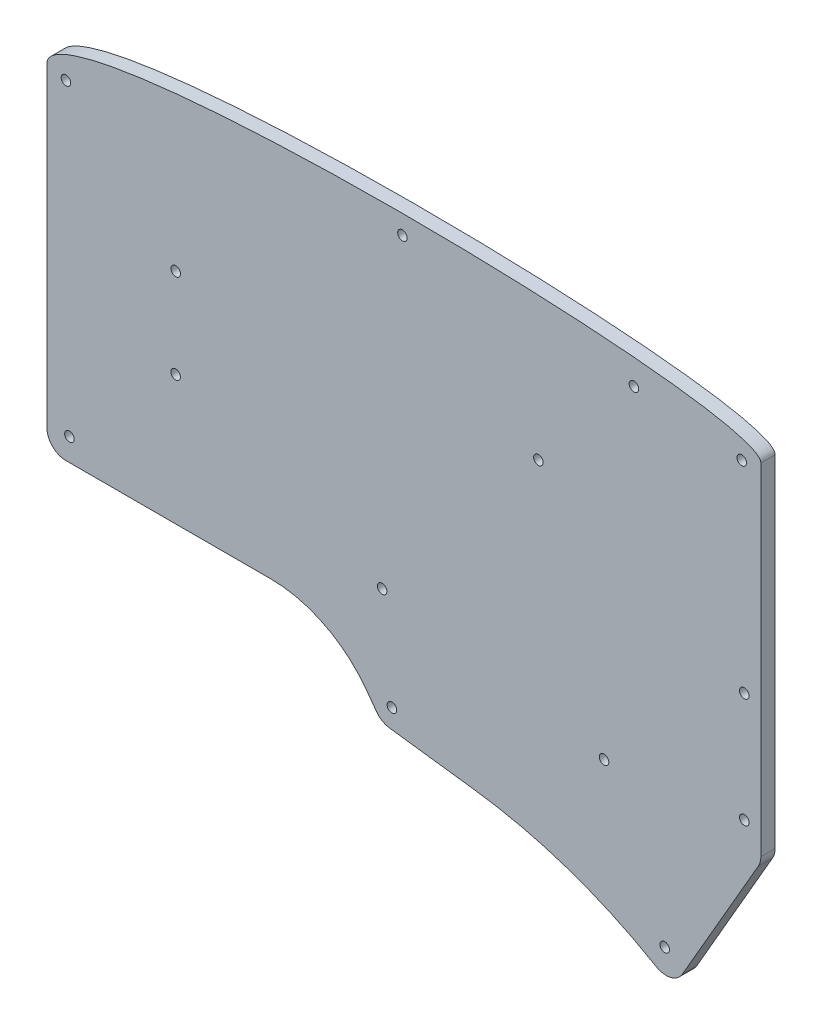
SolidWorks part; units mm, degrees
ref_plane "Front Plane" through (0, 0, 0) normal (0, 0, 1) x (1, 0, 0)
ref_plane "Top Plane" through (0, 0, 0) normal (0, 1, 0) x (1, 0, 0)
ref_plane "Right Plane" through (0, 0, 0) normal (1, 0, 0) x (0, 0, -1)
sketch "Model" plane through (0, 0, 0) normal (0, 0, 1) x (1, 0, 0)
  line L0 (-21.8431, 7.4481) -> (-8.6148, 30.3792)
  line L1 (-38.0636, 15.3297) -> (-23.771, 7.0696)
  line L2 (-75.3888, 20.2293) -> (-38.7189, 15.4592)
  line L3 (-86.2854, 34.8343) -> (-75.7419, 20.3766)
  line L4 (-29.1405, 92.9799) -> (-29.1405, 91.7303)
  line L5 (-8.8891, 91.2299) -> (-28.6402, 91.2299)
  line L6 (-8.3888, 90.7295) -> (-8.3888, 31.2555)
  line L7 (-86.6385, 34.9791) -> (-141.6396, 34.9791)
  line L8 (-142.1399, 90.7295) -> (-142.1399, 35.4795)
  line L9 (-104.6394, 91.2299) -> (-141.6396, 91.2299)
  line L10 (-104.139, 95.4793) -> (-104.139, 91.7303)
  line L11 (-85.6402, 95.9797) -> (-103.6387, 95.9797)
  line L12 (-85.1399, 97.7297) -> (-85.1399, 96.4801)
  line L13 (-67.6393, 98.2301) -> (-84.6395, 98.2301)
  line L14 (-67.1389, 96.4801) -> (-67.1389, 97.7297)
  line L15 (-48.6401, 95.9797) -> (-66.6385, 95.9797)
  line L16 (-48.1397, 93.9807) -> (-48.1397, 95.4793)
  line L17 (-29.6384, 93.4803) -> (-47.6393, 93.4803)
  line L18 (135.1563, 30.6526) -> (116.2359, 41.5721)
  line L19 (123.1828, 7.2669) -> (135.5373, 28.7222)
  line L20 (106.9623, 15.1485) -> (121.2549, 6.8884)
  line L21 (69.6371, 20.0481) -> (106.307, 15.278)
  line L22 (58.7405, 34.6531) -> (69.284, 20.1955)
  line L23 (115.8854, 92.7987) -> (115.8828, 42.2376)
  line L24 (58.3874, 34.7979) -> (3.3863, 34.7979)
  line L25 (2.886, 90.5483) -> (2.886, 35.2983)
  line L26 (40.3865, 91.0487) -> (3.3863, 91.0487)
  line L27 (40.8869, 95.2981) -> (40.8869, 91.5491)
  line L28 (59.3857, 95.7985) -> (41.3872, 95.7985)
  line L29 (59.886, 97.5485) -> (59.886, 96.2989)
  line L30 (77.3866, 98.0489) -> (60.3864, 98.0489)
  line L31 (77.887, 96.2989) -> (77.887, 97.5485)
  line L32 (96.3858, 95.7985) -> (78.3874, 95.7985)
  line L33 (96.8862, 93.7995) -> (96.8862, 95.2981)
  line L34 (115.3875, 93.2991) -> (97.3866, 93.2991)
  line L35 (20.1915, -96.2476) -> (6.9631, -73.3165)
  line L36 (36.4119, -88.366) -> (22.1193, -96.6261)
  line L37 (73.7371, -83.4663) -> (37.0672, -88.2365)
  line L38 (84.6337, -68.8614) -> (74.0902, -83.319)
  line L39 (27.4889, -10.7157) -> (27.4889, -11.9654)
  line L40 (7.2375, -12.4658) -> (26.9885, -12.4658)
  line L41 (6.7371, -12.9662) -> (6.7371, -72.4402)
  line L42 (84.9868, -68.7166) -> (139.9879, -68.7166)
  line L43 (140.4883, -12.9662) -> (140.4883, -68.2162)
  line L44 (102.9878, -12.4658) -> (139.9879, -12.4658)
  line L45 (102.4874, -8.2164) -> (102.4874, -11.9654)
  line L46 (83.9886, -7.716) -> (101.987, -7.716)
  line L47 (83.4882, -5.9659) -> (83.4882, -7.2156)
  line L48 (65.9876, -5.4656) -> (82.9878, -5.4656)
  line L49 (65.4872, -7.2156) -> (65.4872, -5.9659)
  line L50 (46.9884, -7.716) -> (64.9869, -7.716)
  line L51 (46.488, -9.715) -> (46.488, -8.2164)
  line L52 (27.9867, -10.2154) -> (45.9877, -10.2154)
  line L53 (-136.808, -73.043) -> (-117.8876, -62.1236)
  line L54 (-124.8344, -96.4288) -> (-137.189, -74.9734)
  line L55 (-108.614, -88.5472) -> (-122.9066, -96.8073)
  line L56 (-71.2888, -83.6475) -> (-107.9587, -88.4176)
  line L57 (-60.3922, -69.0425) -> (-70.9357, -83.5002)
  line L58 (-117.537, -10.8969) -> (-117.5345, -61.4581)
  line L59 (-60.0391, -68.8978) -> (-5.038, -68.8978)
  line L60 (-4.5376, -13.1474) -> (-4.5376, -68.3974)
  line L61 (-42.0381, -12.647) -> (-5.038, -12.647)
  line L62 (-42.5385, -8.3976) -> (-42.5385, -12.1466)
  line L63 (-61.0373, -7.8972) -> (-43.0389, -7.8972)
  line L64 (-61.5377, -6.1471) -> (-61.5377, -7.3968)
  line L65 (-79.0383, -5.6467) -> (-62.0381, -5.6467)
  line L66 (-79.5387, -7.3968) -> (-79.5387, -6.1471)
  line L67 (-98.0375, -7.8972) -> (-80.039, -7.8972)
  line L68 (-98.5378, -9.8962) -> (-98.5378, -8.3976)
  line L69 (-117.0392, -10.3965) -> (-99.0382, -10.3965)
  line L70 (138.9148, 92.1117) -> (138.9148, 33.3582)
  line L71 (138.1649, 32.9251) -> (119.446, 43.7282)
  line L72 (119.196, 44.1613) -> (119.196, 92.1092)
  line L73 (119.6959, 92.6092) -> (138.4148, 92.6117)
  line L74 (-140.5665, -11.584) -> (-140.5665, -70.3375)
  line L75 (-139.8166, -70.7706) -> (-121.0977, -59.9674)
  line L76 (-120.8476, -59.5344) -> (-120.8476, -11.5865)
  line L77 (-121.3476, -11.0865) -> (-140.0664, -11.084)
  line L78 (18.8966, 74.9256) -> (4.8966, 74.9256)
  line L79 (4.8966, 74.9256) -> (4.8966, 88.9256)
  line L80 (4.8966, 88.9256) -> (18.8966, 88.9256)
  line L81 (18.8966, 88.9256) -> (18.8966, 74.9256)
  line L82 (18.8966, 55.9256) -> (4.8966, 55.9256)
  line L83 (4.8966, 55.9256) -> (4.8966, 69.9256)
  line L84 (4.8966, 69.9256) -> (18.8966, 69.9256)
  line L85 (18.8966, 69.9256) -> (18.8966, 55.9256)
  line L86 (18.8966, 36.9256) -> (4.8966, 36.9256)
  line L87 (4.8966, 36.9256) -> (4.8966, 50.9256)
  line L88 (4.8966, 50.9256) -> (18.8966, 50.9256)
  line L89 (18.8966, 50.9256) -> (18.8966, 36.9256)
  line L90 (37.8948, 74.9262) -> (23.8948, 74.9262)
  line L91 (23.8948, 74.9262) -> (23.8948, 88.9262)
  line L92 (23.8948, 88.9262) -> (37.8948, 88.9262)
  line L93 (37.8948, 88.9262) -> (37.8948, 74.9262)
  line L94 (37.8948, 55.9262) -> (23.8948, 55.9262)
  line L95 (23.8948, 55.9262) -> (23.8948, 69.9262)
  line L96 (23.8948, 69.9262) -> (37.8948, 69.9262)
  line L97 (37.8948, 69.9262) -> (37.8948, 55.9262)
  line L98 (37.8948, 36.9262) -> (23.8948, 36.9262)
  line L99 (23.8948, 36.9262) -> (23.8948, 50.9262)
  line L100 (23.8948, 50.9262) -> (37.8948, 50.9262)
  line L101 (37.8948, 50.9262) -> (37.8948, 36.9262)
  line L102 (56.895, 79.671) -> (42.895, 79.671)
  line L103 (42.895, 79.671) -> (42.895, 93.671)
  line L104 (42.895, 93.671) -> (56.895, 93.671)
  line L105 (56.895, 93.671) -> (56.895, 79.671)
  line L106 (56.895, 60.6711) -> (42.895, 60.6711)
  line L107 (42.895, 60.6711) -> (42.895, 74.6711)
  line L108 (42.895, 74.6711) -> (56.895, 74.6711)
  line L109 (56.895, 74.6711) -> (56.895, 60.6711)
  line L110 (56.895, 41.6711) -> (42.895, 41.6711)
  line L111 (42.895, 41.6711) -> (42.895, 55.6711)
  line L112 (42.895, 55.6711) -> (56.895, 55.6711)
  line L113 (56.895, 55.6711) -> (56.895, 41.6711)
  line L114 (75.897, 82.0499) -> (61.897, 82.0499)
  line L115 (61.897, 82.0499) -> (61.897, 96.0499)
  line L116 (61.897, 96.0499) -> (75.897, 96.0499)
  line L117 (75.897, 96.0499) -> (75.897, 82.0499)
  line L118 (75.897, 63.0499) -> (61.897, 63.0499)
  line L119 (61.897, 63.0499) -> (61.897, 77.0499)
  line L120 (61.897, 77.0499) -> (75.897, 77.0499)
  line L121 (75.897, 77.0499) -> (75.897, 63.0499)
  line L122 (75.897, 44.0499) -> (61.897, 44.0499)
  line L123 (61.897, 44.0499) -> (61.897, 58.0499)
  line L124 (61.897, 58.0499) -> (75.897, 58.0499)
  line L125 (75.897, 58.0499) -> (75.897, 44.0499)
  line L126 (94.8982, 79.6753) -> (80.8982, 79.6753)
  line L127 (80.8982, 79.6753) -> (80.8982, 93.6753)
  line L128 (80.8982, 93.6753) -> (94.8982, 93.6753)
  line L129 (94.8982, 93.6753) -> (94.8982, 79.6753)
  line L130 (94.8982, 60.6753) -> (80.8982, 60.6753)
  line L131 (80.8982, 60.6753) -> (80.8982, 74.6753)
  line L132 (80.8982, 74.6753) -> (94.8982, 74.6753)
  line L133 (94.8982, 74.6753) -> (94.8982, 60.6753)
  line L134 (94.8982, 41.6753) -> (80.8982, 41.6753)
  line L135 (80.8982, 41.6753) -> (80.8982, 55.6753)
  line L136 (80.8982, 55.6753) -> (94.8982, 55.6753)
  line L137 (94.8982, 55.6753) -> (94.8982, 41.6753)
  line L138 (113.9, 77.2905) -> (99.9, 77.2905)
  line L139 (99.9, 77.2905) -> (99.9, 91.2905)
  line L140 (99.9, 91.2905) -> (113.9, 91.2905)
  line L141 (113.9, 91.2905) -> (113.9, 77.2905)
  line L142 (113.9, 58.2905) -> (99.9, 58.2905)
  line L143 (99.9, 58.2905) -> (99.9, 72.2905)
  line L144 (99.9, 72.2905) -> (113.9, 72.2905)
  line L145 (113.9, 72.2905) -> (113.9, 58.2905)
  line L146 (113.9, 39.2905) -> (99.9, 39.2905)
  line L147 (99.9, 39.2905) -> (99.9, 53.2905)
  line L148 (99.9, 53.2905) -> (113.9, 53.2905)
  line L149 (113.9, 53.2905) -> (113.9, 39.2905)
  line L150 (85.4166, 22.0174) -> (71.4166, 22.0174)
  line L151 (71.4166, 22.0174) -> (71.4166, 36.0174)
  line L152 (71.4166, 36.0174) -> (85.4166, 36.0174)
  line L153 (85.4166, 36.0174) -> (85.4166, 22.0174)
  line L154 (104.3289, 17.734) -> (90.806, 21.3575)
  line L155 (90.806, 21.3575) -> (94.4294, 34.8805)
  line L156 (94.4294, 34.8805) -> (107.9524, 31.257)
  line L157 (107.9524, 31.257) -> (104.3289, 17.734)
  line L158 (124.1994, 13.0049) -> (112.075, 20.0049)
  line L159 (112.075, 20.0049) -> (119.075, 32.1293)
  line L160 (119.075, 32.1293) -> (131.1994, 25.1293)
  line L161 (131.1994, 25.1293) -> (124.1994, 13.0049)
  line L162 (-20.5483, -28.7701) -> (-6.5483, -28.7701)
  line L163 (-6.5483, -28.7701) -> (-6.5483, -14.7701)
  line L164 (-6.5483, -14.7701) -> (-20.5483, -14.7701)
  line L165 (-20.5483, -14.7701) -> (-20.5483, -28.7701)
  line L166 (-20.5483, -47.7701) -> (-6.5483, -47.7701)
  line L167 (-6.5483, -47.7701) -> (-6.5483, -33.7701)
  line L168 (-6.5483, -33.7701) -> (-20.5483, -33.7701)
  line L169 (-20.5483, -33.7701) -> (-20.5483, -47.7701)
  line L170 (-20.5483, -66.7701) -> (-6.5483, -66.7701)
  line L171 (-6.5483, -66.7701) -> (-6.5483, -52.7701)
  line L172 (-6.5483, -52.7701) -> (-20.5483, -52.7701)
  line L173 (-20.5483, -52.7701) -> (-20.5483, -66.7701)
  line L174 (-39.5464, -28.7694) -> (-25.5464, -28.7694)
  line L175 (-25.5464, -28.7694) -> (-25.5464, -14.7694)
  line L176 (-25.5464, -14.7694) -> (-39.5464, -14.7694)
  line L177 (-39.5464, -14.7694) -> (-39.5464, -28.7694)
  line L178 (-39.5464, -47.7694) -> (-25.5464, -47.7694)
  line L179 (-25.5464, -47.7694) -> (-25.5464, -33.7694)
  line L180 (-25.5464, -33.7694) -> (-39.5464, -33.7694)
  line L181 (-39.5464, -33.7694) -> (-39.5464, -47.7694)
  line L182 (-39.5464, -66.7694) -> (-25.5464, -66.7694)
  line L183 (-25.5464, -66.7694) -> (-25.5464, -52.7694)
  line L184 (-25.5464, -52.7694) -> (-39.5464, -52.7694)
  line L185 (-39.5464, -52.7694) -> (-39.5464, -66.7694)
  line L186 (-58.5467, -24.0246) -> (-44.5467, -24.0246)
  line L187 (-44.5467, -24.0246) -> (-44.5467, -10.0246)
  line L188 (-44.5467, -10.0246) -> (-58.5467, -10.0246)
  line L189 (-58.5467, -10.0246) -> (-58.5467, -24.0246)
  line L190 (-58.5467, -43.0246) -> (-44.5467, -43.0246)
  line L191 (-44.5467, -43.0246) -> (-44.5467, -29.0246)
  line L192 (-44.5467, -29.0246) -> (-58.5467, -29.0246)
  line L193 (-58.5467, -29.0246) -> (-58.5467, -43.0246)
  line L194 (-58.5467, -62.0246) -> (-44.5467, -62.0246)
  line L195 (-44.5467, -62.0246) -> (-44.5467, -48.0246)
  line L196 (-44.5467, -48.0246) -> (-58.5467, -48.0246)
  line L197 (-58.5467, -48.0246) -> (-58.5467, -62.0246)
  line L198 (-77.5486, -21.6458) -> (-63.5486, -21.6458)
  line L199 (-63.5486, -21.6458) -> (-63.5486, -7.6458)
  line L200 (-63.5486, -7.6458) -> (-77.5486, -7.6458)
  line L201 (-77.5486, -7.6458) -> (-77.5486, -21.6458)
  line L202 (-77.5486, -40.6458) -> (-63.5486, -40.6458)
  line L203 (-63.5486, -40.6458) -> (-63.5486, -26.6458)
  line L204 (-63.5486, -26.6458) -> (-77.5486, -26.6458)
  line L205 (-77.5486, -26.6458) -> (-77.5486, -40.6458)
  line L206 (-77.5486, -59.6458) -> (-63.5486, -59.6458)
  line L207 (-63.5486, -59.6458) -> (-63.5486, -45.6458)
  line L208 (-63.5486, -45.6458) -> (-77.5486, -45.6458)
  line L209 (-77.5486, -45.6458) -> (-77.5486, -59.6458)
  line L210 (-96.5499, -24.0204) -> (-82.5499, -24.0204)
  line L211 (-82.5499, -24.0204) -> (-82.5499, -10.0204)
  line L212 (-82.5499, -10.0204) -> (-96.5499, -10.0204)
  line L213 (-96.5499, -10.0204) -> (-96.5499, -24.0204)
  line L214 (-96.5499, -43.0203) -> (-82.5499, -43.0203)
  line L215 (-82.5499, -43.0203) -> (-82.5499, -29.0203)
  line L216 (-82.5499, -29.0203) -> (-96.5499, -29.0203)
  line L217 (-96.5499, -29.0203) -> (-96.5499, -43.0203)
  line L218 (-96.5499, -62.0203) -> (-82.5499, -62.0203)
  line L219 (-82.5499, -62.0203) -> (-82.5499, -48.0203)
  line L220 (-82.5499, -48.0203) -> (-96.5499, -48.0203)
  line L221 (-96.5499, -48.0203) -> (-96.5499, -62.0203)
  line L222 (-115.5516, -26.4052) -> (-101.5516, -26.4052)
  line L223 (-101.5516, -26.4052) -> (-101.5516, -12.4052)
  line L224 (-101.5516, -12.4052) -> (-115.5516, -12.4052)
  line L225 (-115.5516, -12.4052) -> (-115.5516, -26.4052)
  line L226 (-115.5516, -45.4052) -> (-101.5516, -45.4052)
  line L227 (-101.5516, -45.4052) -> (-101.5516, -31.4052)
  line L228 (-101.5516, -31.4052) -> (-115.5516, -31.4052)
  line L229 (-115.5516, -31.4052) -> (-115.5516, -45.4052)
  line L230 (-115.5516, -64.4052) -> (-101.5516, -64.4052)
  line L231 (-101.5516, -64.4052) -> (-101.5516, -50.4052)
  line L232 (-101.5516, -50.4052) -> (-115.5516, -50.4052)
  line L233 (-115.5516, -50.4052) -> (-115.5516, -64.4052)
  line L234 (-87.0683, -81.6783) -> (-73.0683, -81.6783)
  line L235 (-73.0683, -81.6783) -> (-73.0683, -67.6783)
  line L236 (-73.0683, -67.6783) -> (-87.0683, -67.6783)
  line L237 (-87.0683, -67.6783) -> (-87.0683, -81.6783)
  line L238 (-105.9806, -85.9616) -> (-92.4576, -82.3382)
  line L239 (-92.4576, -82.3382) -> (-96.0811, -68.8152)
  line L240 (-96.0811, -68.8152) -> (-109.6041, -72.4387)
  line L241 (-109.6041, -72.4387) -> (-105.9806, -85.9616)
  line L242 (-125.851, -90.6908) -> (-113.7267, -83.6908)
  line L243 (-113.7267, -83.6908) -> (-120.7267, -71.5664)
  line L244 (-120.7267, -71.5664) -> (-132.851, -78.5664)
  line L245 (-132.851, -78.5664) -> (-125.851, -90.6908)
  spline S0 degree 3 poles (-8.6153, 30.3807) (-8.4626, 30.6458) (-8.3842, 30.9472) (-8.3882, 31.2532) knots 0 0 0 0 1 1 1 1
  spline S1 degree 3 poles (-21.8439, 7.4422) (-21.8429, 7.4437) (-21.8419, 7.4453) (-21.8408, 7.4468) knots 1 1 1 1 2 2 2 2
  spline S2 degree 3 poles (-23.769, 7.0673) (-23.1339, 6.6392) (-22.272, 6.8071) (-21.8439, 7.4422) knots 0 0 0 0 1 1 1 1
  spline S3 degree 3 poles (-38.063, 15.3284) (-38.2765, 15.3928) (-38.4957, 15.4362) (-38.7176, 15.4579) knots 0 0 0 0 1 1 1 1
  spline S4 degree 3 poles (-75.7416, 20.3746) (-75.6478, 20.2809) (-75.5206, 20.2283) (-75.3881, 20.2283) knots 0 0 0 0 1 1 1 1
  spline S5 degree 3 poles (-29.1383, 92.9782) (-29.1382, 93.2543) (-29.362, 93.4782) (-29.6381, 93.4783) knots 0 0 0 0 1 1 1 1
  spline S6 degree 3 poles (-29.1383, 91.7282) (-29.1383, 91.4521) (-28.9145, 91.2282) (-28.6384, 91.2281) (-28.6383, 91.2281) (-28.6382, 91.2281) (-28.6381, 91.2281) knots 0 0 0 0 1 1 1 2 2 2 2
  spline S7 degree 3 poles (-86.2846, 34.8318) (-86.3784, 34.9256) (-86.5056, 34.9783) (-86.6385, 34.9791) knots 0 0 0 0 1 1 1 1
  spline S8 degree 3 poles (-142.1382, 35.4782) (-142.1381, 35.2021) (-141.9142, 34.9783) (-141.6381, 34.9783) knots 0 0 0 0 1 1 1 1
  spline S9 degree 3 poles (-141.638, 91.2281) (-141.9142, 91.2282) (-142.1381, 91.0044) (-142.1382, 90.7282) knots 0 0 0 0 1 1 1 1
  spline S10 degree 3 poles (-104.6382, 91.2281) (-104.362, 91.228) (-104.1381, 91.4518) (-104.138, 91.728) (-104.138, 91.7281) (-104.138, 91.7281) (-104.138, 91.7282) knots 0 0 0 0 1 1 1 2 2 2 2
  spline S11 degree 3 poles (-103.6382, 95.9781) (-103.9142, 95.9781) (-104.138, 95.7543) (-104.138, 95.4783) knots 0 0 0 0 1 1 1 1
  spline S12 degree 3 poles (-85.6382, 95.9781) (-85.3621, 95.9781) (-85.1382, 96.2019) (-85.1381, 96.478) (-85.1381, 96.4781) (-85.1381, 96.4782) (-85.1381, 96.4783) knots 0 0 0 0 1 1 1 2 2 2 2
  spline S13 degree 3 poles (-84.6382, 98.2283) (-84.9144, 98.2283) (-85.1382, 98.0044) (-85.1381, 97.7282) knots 0 0 0 0 1 1 1 1
  spline S14 degree 3 poles (-67.1381, 97.7282) (-67.1381, 98.0043) (-67.3619, 98.2283) (-67.638, 98.2283) knots 0 0 0 0 2 2 2 2
  spline S15 degree 3 poles (-67.1381, 96.4783) (-67.1382, 96.2021) (-66.9144, 95.9782) (-66.6383, 95.9781) (-66.6382, 95.9781) (-66.6381, 95.9781) (-66.638, 95.9781) knots 0 0 0 0 1 1 1 2 2 2 2
  spline S16 degree 3 poles (-48.1382, 95.4783) (-48.1383, 95.7543) (-48.362, 95.9781) (-48.6381, 95.9781) knots 0 0 0 0 1 1 1 1
  spline S17 degree 3 poles (-48.1382, 93.9782) (-48.1381, 93.702) (-47.9142, 93.4782) (-47.6381, 93.4783) knots 0 0 0 0 1 1 1 1
  spline S18 degree 3 poles (-8.3882, 90.7282) (-8.3883, 91.0043) (-8.6121, 91.228) (-8.8881, 91.2281) knots 0 0 0 0 1 1 1 1
  spline S19 degree 3 poles (115.8851, 42.2368) (115.8929, 41.9725) (116.0232, 41.7268) (116.2377, 41.5721) knots 0 0 0 0 1 1 1 1
  spline S20 degree 3 poles (135.163, 30.647) (135.1614, 30.648) (135.1599, 30.6491) (135.1583, 30.6501) knots 1 1 1 1 2 2 2 2
  spline S21 degree 3 poles (135.5373, 28.7222) (135.9659, 29.3571) (135.7981, 30.2189) (135.163, 30.647) knots 0 0 0 0 1 1 1 1
  spline S22 degree 3 poles (123.182, 7.261) (123.183, 7.2625) (123.184, 7.2641) (123.1851, 7.2656) knots 1 1 1 1 2 2 2 2
  spline S23 degree 3 poles (121.2569, 6.8861) (121.892, 6.4581) (122.7539, 6.6259) (123.182, 7.261) knots 0 0 0 0 1 1 1 1
  spline S24 degree 3 poles (106.9629, 15.1472) (106.7494, 15.2117) (106.5302, 15.255) (106.3083, 15.2768) knots 0 0 0 0 1 1 1 1
  spline S25 degree 3 poles (69.2843, 20.1934) (69.3781, 20.0997) (69.5053, 20.0471) (69.6378, 20.0471) knots 0 0 0 0 1 1 1 1
  spline S26 degree 3 poles (115.8876, 92.797) (115.8877, 93.0731) (115.6639, 93.297) (115.3878, 93.2971) knots 0 0 0 0 1 1 1 1
  spline S27 degree 3 poles (58.7413, 34.6506) (58.6475, 34.7444) (58.5203, 34.7971) (58.3874, 34.7979) knots 0 0 0 0 1 1 1 1
  spline S28 degree 3 poles (2.8877, 35.297) (2.8878, 35.0209) (3.1117, 34.7971) (3.3878, 34.7971) knots 0 0 0 0 1 1 1 1
  spline S29 degree 3 poles (3.3879, 91.0469) (3.1117, 91.047) (2.8878, 90.8232) (2.8877, 90.547) knots 0 0 0 0 1 1 1 1
  spline S30 degree 3 poles (40.3877, 91.0469) (40.6639, 91.0468) (40.8878, 91.2706) (40.8879, 91.5468) (40.8879, 91.5469) (40.8879, 91.5469) (40.8879, 91.547) knots 0 0 0 0 1 1 1 2 2 2 2
  spline S31 degree 3 poles (41.3877, 95.797) (41.1117, 95.7969) (40.8879, 95.5731) (40.8879, 95.2971) knots 0 0 0 0 1 1 1 1
  spline S32 degree 3 poles (59.3877, 95.797) (59.6638, 95.7969) (59.8877, 96.0207) (59.8878, 96.2968) (59.8878, 96.2969) (59.8878, 96.297) (59.8878, 96.2971) knots 0 0 0 0 1 1 1 2 2 2 2
  spline S33 degree 3 poles (60.3877, 98.0471) (60.1115, 98.0471) (59.8877, 97.8232) (59.8878, 97.547) knots 0 0 0 0 1 1 1 1
  spline S34 degree 3 poles (77.8878, 97.547) (77.8878, 97.8232) (77.664, 98.0471) (77.3879, 98.0471) knots 0 0 0 0 2 2 2 2
  spline S35 degree 3 poles (77.8878, 96.2971) (77.8877, 96.0209) (78.1115, 95.797) (78.3876, 95.797) (78.3877, 95.797) (78.3878, 95.797) (78.3879, 95.797) knots 0 0 0 0 1 1 1 2 2 2 2
  spline S36 degree 3 poles (96.8877, 95.2971) (96.8876, 95.5731) (96.6639, 95.7969) (96.3878, 95.797) knots 0 0 0 0 1 1 1 1
  spline S37 degree 3 poles (96.8877, 93.797) (96.8878, 93.5208) (97.1117, 93.297) (97.3878, 93.2971) knots 0 0 0 0 1 1 1 1
  spline S38 degree 3 poles (6.9637, -73.315) (6.8109, -73.0499) (6.7325, -72.7484) (6.7366, -72.4425) knots 0 0 0 0 1 1 1 1
  spline S39 degree 3 poles (20.1923, -96.2535) (20.1912, -96.252) (20.1902, -96.2504) (20.1892, -96.2489) knots 1 1 1 1 2 2 2 2
  spline S40 degree 3 poles (22.1173, -96.6284) (21.4822, -97.0564) (20.6203, -96.8886) (20.1923, -96.2535) knots 0 0 0 0 1 1 1 1
  spline S41 degree 3 poles (36.4114, -88.3673) (36.6248, -88.3028) (36.844, -88.2594) (37.0659, -88.2377) knots 0 0 0 0 1 1 1 1
  spline S42 degree 3 poles (74.0899, -83.3211) (73.9962, -83.4148) (73.869, -83.4674) (73.7364, -83.4674) knots 0 0 0 0 1 1 1 1
  spline S43 degree 3 poles (27.4866, -10.7175) (27.4865, -10.4414) (27.7103, -10.2175) (27.9865, -10.2174) knots 0 0 0 0 1 1 1 1
  spline S44 degree 3 poles (27.4866, -11.9674) (27.4866, -12.2436) (27.2628, -12.4675) (26.9867, -12.4676) (26.9866, -12.4676) (26.9865, -12.4676) (26.9865, -12.4676) knots 0 0 0 0 1 1 1 2 2 2 2
  spline S45 degree 3 poles (84.633, -68.8639) (84.7267, -68.7701) (84.8539, -68.7174) (84.9868, -68.7166) knots 0 0 0 0 1 1 1 1
  spline S46 degree 3 poles (140.4865, -68.2175) (140.4864, -68.4936) (140.2625, -68.7174) (139.9864, -68.7173) knots 0 0 0 0 1 1 1 1
  spline S47 degree 3 poles (139.9864, -12.4676) (140.2625, -12.4675) (140.4864, -12.6913) (140.4865, -12.9674) knots 0 0 0 0 1 1 1 1
  spline S48 degree 3 poles (102.9865, -12.4676) (102.7103, -12.4676) (102.4864, -12.2438) (102.4864, -11.9677) (102.4864, -11.9676) (102.4864, -11.9675) (102.4864, -11.9674) knots 0 0 0 0 1 1 1 2 2 2 2
  spline S49 degree 3 poles (101.9865, -7.7175) (102.2625, -7.7176) (102.4863, -7.9413) (102.4864, -8.2174) knots 0 0 0 0 1 1 1 1
  spline S50 degree 3 poles (83.9865, -7.7175) (83.7104, -7.7176) (83.4865, -7.4938) (83.4864, -7.2176) (83.4864, -7.2176) (83.4864, -7.2175) (83.4864, -7.2174) knots 0 0 0 0 1 1 1 2 2 2 2
  spline S51 degree 3 poles (82.9865, -5.4673) (83.2627, -5.4674) (83.4865, -5.6913) (83.4864, -5.9675) knots 0 0 0 0 1 1 1 1
  spline S52 degree 3 poles (65.4865, -5.9675) (65.4864, -5.6913) (65.7102, -5.4674) (65.9863, -5.4673) knots 0 0 0 0 2 2 2 2
  spline S53 degree 3 poles (65.4865, -7.2174) (65.4865, -7.4935) (65.2627, -7.7174) (64.9866, -7.7175) (64.9865, -7.7175) (64.9864, -7.7175) (64.9863, -7.7175) knots 0 0 0 0 1 1 1 2 2 2 2
  spline S54 degree 3 poles (46.4865, -8.2174) (46.4866, -7.9413) (46.7103, -7.7176) (46.9864, -7.7175) knots 0 0 0 0 1 1 1 1
  spline S55 degree 3 poles (46.4865, -9.7175) (46.4865, -9.9937) (46.2625, -10.2175) (45.9864, -10.2174) knots 0 0 0 0 1 1 1 1
  spline S56 degree 3 poles (6.7366, -12.9674) (6.7366, -12.6914) (6.9604, -12.4676) (7.2365, -12.4676) knots 0 0 0 0 1 1 1 1
  spline S57 degree 3 poles (-117.5368, -61.4589) (-117.5446, -61.7232) (-117.6748, -61.9689) (-117.8893, -62.1236) knots 0 0 0 0 1 1 1 1
  spline S58 degree 3 poles (-136.8146, -73.0487) (-136.8131, -73.0476) (-136.8116, -73.0466) (-136.81, -73.0456) knots 1 1 1 1 2 2 2 2
  spline S59 degree 3 poles (-137.189, -74.9734) (-137.6176, -74.3386) (-137.4497, -73.4767) (-136.8146, -73.0487) knots 0 0 0 0 1 1 1 1
  spline S60 degree 3 poles (-124.8336, -96.4347) (-124.8347, -96.4331) (-124.8357, -96.4316) (-124.8367, -96.4301) knots 1 1 1 1 2 2 2 2
  spline S61 degree 3 poles (-122.9086, -96.8095) (-123.5437, -97.2376) (-124.4056, -97.0698) (-124.8336, -96.4347) knots 0 0 0 0 1 1 1 1
  spline S62 degree 3 poles (-108.6145, -88.5485) (-108.4011, -88.484) (-108.1819, -88.4406) (-107.96, -88.4189) knots 0 0 0 0 1 1 1 1
  spline S63 degree 3 poles (-70.936, -83.5022) (-71.0297, -83.596) (-71.1569, -83.6486) (-71.2895, -83.6485) knots 0 0 0 0 1 1 1 1
  spline S64 degree 3 poles (-117.5393, -10.8987) (-117.5394, -10.6226) (-117.3156, -10.3987) (-117.0394, -10.3986) knots 0 0 0 0 1 1 1 1
  spline S65 degree 3 poles (-60.3929, -69.0451) (-60.2992, -68.9513) (-60.172, -68.8986) (-60.0391, -68.8978) knots 0 0 0 0 1 1 1 1
  spline S66 degree 3 poles (-4.5394, -68.3987) (-4.5395, -68.6748) (-4.7634, -68.8986) (-5.0395, -68.8985) knots 0 0 0 0 1 1 1 1
  spline S67 degree 3 poles (-5.0395, -12.6488) (-4.7634, -12.6487) (-4.5395, -12.8725) (-4.5394, -13.1486) knots 0 0 0 0 1 1 1 1
  spline S68 degree 3 poles (-42.0394, -12.6488) (-42.3156, -12.6488) (-42.5395, -12.425) (-42.5395, -12.1489) (-42.5395, -12.1488) (-42.5395, -12.1487) (-42.5395, -12.1486) knots 0 0 0 0 1 1 1 2 2 2 2
  spline S69 degree 3 poles (-43.0394, -7.8987) (-42.7634, -7.8988) (-42.5396, -8.1225) (-42.5395, -8.3986) knots 0 0 0 0 1 1 1 1
  spline S70 degree 3 poles (-61.0394, -7.8987) (-61.3155, -7.8988) (-61.5394, -7.675) (-61.5395, -7.3988) (-61.5395, -7.3988) (-61.5395, -7.3987) (-61.5395, -7.3986) knots 0 0 0 0 1 1 1 2 2 2 2
  spline S71 degree 3 poles (-62.0394, -5.6485) (-61.7632, -5.6486) (-61.5394, -5.8725) (-61.5395, -6.1486) knots 0 0 0 0 1 1 1 1
  spline S72 degree 3 poles (-79.5394, -6.1486) (-79.5395, -5.8725) (-79.3157, -5.6486) (-79.0396, -5.6485) knots 0 0 0 0 2 2 2 2
  spline S73 degree 3 poles (-79.5394, -7.3986) (-79.5394, -7.6747) (-79.7632, -7.8986) (-80.0393, -7.8987) (-80.0394, -7.8987) (-80.0395, -7.8987) (-80.0396, -7.8987) knots 0 0 0 0 1 1 1 2 2 2 2
  spline S74 degree 3 poles (-98.5394, -8.3986) (-98.5393, -8.1225) (-98.3156, -7.8988) (-98.0395, -7.8987) knots 0 0 0 0 1 1 1 1
  spline S75 degree 3 poles (-98.5394, -9.8987) (-98.5394, -10.1748) (-98.7634, -10.3986) (-99.0395, -10.3986) knots 0 0 0 0 1 1 1 1
  spline S76 degree 3 poles (-123.6381, 52.6314) (-124.2456, 52.6314) (-124.7381, 53.1239) (-124.7381, 53.7314) (-124.7381, 54.3389) (-124.2456, 54.8314) (-123.6381, 54.8314) knots 2 2 2 2 3 3 3 4 4 4 4
  spline S77 degree 3 poles (-123.6381, 54.8314) (-123.0306, 54.8314) (-122.5381, 54.3389) (-122.5381, 53.7314) (-122.5381, 53.1239) (-123.0306, 52.6314) (-123.6381, 52.6314) knots 0 0 0 0 1 1 1 2 2 2 2
  spline S78 degree 3 poles (-123.6381, 71.3814) (-124.2456, 71.3814) (-124.7381, 71.8739) (-124.7381, 72.4814) (-124.7381, 73.0889) (-124.2456, 73.5814) (-123.6381, 73.5814) knots 2 2 2 2 3 3 3 4 4 4 4
  spline S79 degree 3 poles (-123.6381, 73.5814) (-123.0306, 73.5814) (-122.5381, 73.0889) (-122.5381, 72.4814) (-122.5381, 71.8739) (-123.0306, 71.3814) (-123.6381, 71.3814) knots 0 0 0 0 1 1 1 2 2 2 2
  spline S80 degree 3 poles (-47.6381, 75.1312) (-48.2456, 75.1312) (-48.7381, 75.6237) (-48.7381, 76.2312) (-48.7381, 76.8387) (-48.2456, 77.3312) (-47.6381, 77.3312) knots 2 2 2 2 3 3 3 4 4 4 4
  spline S81 degree 3 poles (-47.6381, 77.3312) (-47.0306, 77.3312) (-46.5381, 76.8387) (-46.5381, 76.2312) (-46.5381, 75.6237) (-47.0306, 75.1312) (-47.6381, 75.1312) knots 0 0 0 0 1 1 1 2 2 2 2
  spline S82 degree 3 poles (-80.388, 35.3813) (-80.9956, 35.3813) (-81.488, 35.8738) (-81.488, 36.4813) (-81.488, 37.0888) (-80.9956, 37.5813) (-80.388, 37.5813) knots 2 2 2 2 3 3 3 4 4 4 4
  spline S83 degree 3 poles (-80.388, 37.5813) (-79.7805, 37.5813) (-79.288, 37.0888) (-79.288, 36.4813) (-79.288, 35.8738) (-79.7805, 35.3813) (-80.388, 35.3813) knots 0 0 0 0 1 1 1 2 2 2 2
  spline S84 degree 3 poles (-33.8881, 27.6312) (-34.4956, 27.6312) (-34.9881, 28.1237) (-34.9881, 28.7312) (-34.9881, 29.3388) (-34.4956, 29.8312) (-33.8881, 29.8312) knots 2 2 2 2 3 3 3 4 4 4 4
  spline S85 degree 3 poles (-33.8881, 29.8312) (-33.2805, 29.8312) (-32.7881, 29.3388) (-32.7881, 28.7312) (-32.7881, 28.1237) (-33.2805, 27.6312) (-33.8881, 27.6312) knots 0 0 0 0 1 1 1 2 2 2 2
  spline S86 degree 3 poles (21.3878, 52.4502) (20.7803, 52.4502) (20.2878, 52.9427) (20.2878, 53.5502) (20.2878, 54.1578) (20.7803, 54.6502) (21.3878, 54.6502) knots 2 2 2 2 3 3 3 4 4 4 4
  spline S87 degree 3 poles (21.3878, 54.6502) (21.9953, 54.6502) (22.4878, 54.1578) (22.4878, 53.5502) (22.4878, 52.9427) (21.9953, 52.4502) (21.3878, 52.4502) knots 0 0 0 0 1 1 1 2 2 2 2
  spline S88 degree 3 poles (97.3878, 74.95) (96.7803, 74.95) (96.2878, 75.4425) (96.2878, 76.05) (96.2878, 76.6575) (96.7803, 77.15) (97.3878, 77.15) knots 2 2 2 2 3 3 3 4 4 4 4
  spline S89 degree 3 poles (97.3878, 77.15) (97.9953, 77.15) (98.4878, 76.6575) (98.4878, 76.05) (98.4878, 75.4425) (97.9953, 74.95) (97.3878, 74.95) knots 0 0 0 0 1 1 1 2 2 2 2
  spline S90 degree 3 poles (64.6379, 35.2001) (64.0303, 35.2001) (63.5379, 35.6926) (63.5379, 36.3001) (63.5379, 36.9076) (64.0303, 37.4001) (64.6379, 37.4001) knots 2 2 2 2 3 3 3 4 4 4 4
  spline S91 degree 3 poles (64.6379, 37.4001) (65.2454, 37.4001) (65.7379, 36.9076) (65.7379, 36.3001) (65.7379, 35.6926) (65.2454, 35.2001) (64.6379, 35.2001) knots 0 0 0 0 1 1 1 2 2 2 2
  spline S92 degree 3 poles (111.1378, 27.4501) (110.5303, 27.4501) (110.0378, 27.9425) (110.0378, 28.5501) (110.0378, 29.1576) (110.5303, 29.65) (111.1378, 29.65) knots 2 2 2 2 3 3 3 4 4 4 4
  spline S93 degree 3 poles (111.1378, 29.65) (111.7454, 29.65) (112.2378, 29.1576) (112.2378, 28.5501) (112.2378, 27.9425) (111.7454, 27.4501) (111.1378, 27.4501) knots 0 0 0 0 1 1 1 2 2 2 2
  spline S94 degree 3 poles (121.9864, -51.0642) (122.5939, -51.0642) (123.0864, -50.5718) (123.0864, -49.9642) (123.0864, -49.3567) (122.5939, -48.8642) (121.9864, -48.8642) knots 2 2 2 2 3 3 3 4 4 4 4
  spline S95 degree 3 poles (121.9864, -48.8642) (121.3789, -48.8642) (120.8864, -49.3567) (120.8864, -49.9642) (120.8864, -50.5718) (121.3789, -51.0642) (121.9864, -51.0642) knots 0 0 0 0 1 1 1 2 2 2 2
  spline S96 degree 3 poles (121.9864, -32.3142) (122.5939, -32.3142) (123.0864, -31.8218) (123.0864, -31.2142) (123.0864, -30.6067) (122.5939, -30.1142) (121.9864, -30.1142) knots 2 2 2 2 3 3 3 4 4 4 4
  spline S97 degree 3 poles (121.9864, -30.1142) (121.3789, -30.1142) (120.8864, -30.6067) (120.8864, -31.2142) (120.8864, -31.8218) (121.3789, -32.3142) (121.9864, -32.3142) knots 0 0 0 0 1 1 1 2 2 2 2
  spline S98 degree 3 poles (45.9864, -28.5644) (46.5939, -28.5644) (47.0864, -28.072) (47.0864, -27.4644) (47.0864, -26.8569) (46.5939, -26.3644) (45.9864, -26.3644) knots 2 2 2 2 3 3 3 4 4 4 4
  spline S99 degree 3 poles (45.9864, -26.3644) (45.3789, -26.3644) (44.8864, -26.8569) (44.8864, -27.4644) (44.8864, -28.072) (45.3789, -28.5644) (45.9864, -28.5644) knots 0 0 0 0 1 1 1 2 2 2 2
  spline S100 degree 3 poles (78.7364, -68.3144) (79.3439, -68.3144) (79.8364, -67.8219) (79.8364, -67.2144) (79.8364, -66.6069) (79.3439, -66.1144) (78.7364, -66.1144) knots 2 2 2 2 3 3 3 4 4 4 4
  spline S101 degree 3 poles (78.7364, -66.1144) (78.1288, -66.1144) (77.6364, -66.6069) (77.6364, -67.2144) (77.6364, -67.8219) (78.1288, -68.3144) (78.7364, -68.3144) knots 0 0 0 0 1 1 1 2 2 2 2
  spline S102 degree 3 poles (32.2364, -76.0644) (32.8439, -76.0644) (33.3364, -75.5719) (33.3364, -74.9644) (33.3364, -74.3569) (32.8439, -73.8644) (32.2364, -73.8644) knots 2 2 2 2 3 3 3 4 4 4 4
  spline S103 degree 3 poles (32.2364, -73.8644) (31.6289, -73.8644) (31.1364, -74.3569) (31.1364, -74.9644) (31.1364, -75.5719) (31.6289, -76.0644) (32.2364, -76.0644) knots 0 0 0 0 1 1 1 2 2 2 2
  spline S104 degree 3 poles (-23.0395, -51.2454) (-22.432, -51.2454) (-21.9395, -50.7529) (-21.9395, -50.1454) (-21.9395, -49.5379) (-22.432, -49.0454) (-23.0395, -49.0454) knots 2 2 2 2 3 3 3 4 4 4 4
  spline S105 degree 3 poles (-23.0395, -49.0454) (-23.647, -49.0454) (-24.1395, -49.5379) (-24.1395, -50.1454) (-24.1395, -50.7529) (-23.647, -51.2454) (-23.0395, -51.2454) knots 0 0 0 0 1 1 1 2 2 2 2
  spline S106 degree 3 poles (-99.0395, -28.7456) (-98.432, -28.7456) (-97.9395, -28.2531) (-97.9395, -27.6456) (-97.9395, -27.0381) (-98.432, -26.5456) (-99.0395, -26.5456) knots 2 2 2 2 3 3 3 4 4 4 4
  spline S107 degree 3 poles (-99.0395, -26.5456) (-99.647, -26.5456) (-100.1395, -27.0381) (-100.1395, -27.6456) (-100.1395, -28.2531) (-99.647, -28.7456) (-99.0395, -28.7456) knots 0 0 0 0 1 1 1 2 2 2 2
  spline S108 degree 3 poles (-66.2895, -68.4956) (-65.682, -68.4956) (-65.1895, -68.0031) (-65.1895, -67.3956) (-65.1895, -66.7881) (-65.682, -66.2956) (-66.2895, -66.2956) knots 2 2 2 2 3 3 3 4 4 4 4
  spline S109 degree 3 poles (-66.2895, -66.2956) (-66.8971, -66.2956) (-67.3895, -66.7881) (-67.3895, -67.3956) (-67.3895, -68.0031) (-66.8971, -68.4956) (-66.2895, -68.4956) knots 0 0 0 0 1 1 1 2 2 2 2
  spline S110 degree 3 poles (-112.7895, -76.2456) (-112.182, -76.2456) (-111.6895, -75.7531) (-111.6895, -75.1456) (-111.6895, -74.5381) (-112.182, -74.0456) (-112.7895, -74.0456) knots 2 2 2 2 3 3 3 4 4 4 4
  spline S111 degree 3 poles (-112.7895, -74.0456) (-113.397, -74.0456) (-113.8895, -74.5381) (-113.8895, -75.1456) (-113.8895, -75.7531) (-113.397, -76.2456) (-112.7895, -76.2456) knots 0 0 0 0 1 1 1 2 2 2 2
  spline S112 degree 3 poles (138.9148, 33.3582) (138.9148, 32.9733) (138.4982, 32.7327) (138.1649, 32.9251) knots 1 1 1 1 2 2 2 2
  spline S113 degree 3 poles (119.446, 43.7282) (119.2913, 43.8175) (119.196, 43.9826) (119.196, 44.1613) knots 3 3 3 3 4 4 4 4
  spline S114 degree 3 poles (119.196, 92.1092) (119.196, 92.3853) (119.4198, 92.6092) (119.6959, 92.6092) knots 5 5 5 5 6 6 6 6
  spline S115 degree 3 poles (138.4148, 92.6117) (138.6909, 92.6117) (138.9148, 92.3879) (138.9148, 92.1117) knots 7 7 7 7 8 8 8 8
  spline S116 degree 3 poles (-140.5665, -70.3375) (-140.5665, -70.7224) (-140.1499, -70.9629) (-139.8166, -70.7706) knots 1 1 1 1 2 2 2 2
  spline S117 degree 3 poles (-121.0977, -59.9674) (-120.943, -59.8781) (-120.8476, -59.7131) (-120.8476, -59.5344) knots 3 3 3 3 4 4 4 4
  spline S118 degree 3 poles (-120.8476, -11.5865) (-120.8476, -11.3103) (-121.0715, -11.0865) (-121.3476, -11.0865) knots 5 5 5 5 6 6 6 6
  spline S119 degree 3 poles (-140.0664, -11.084) (-140.3426, -11.0839) (-140.5665, -11.3078) (-140.5665, -11.584) knots 7 7 7 7 8 8 8 8
  spline S120 degree 3 poles (120.7443, 45.1272) (120.7443, 45.7347) (121.2368, 46.2272) (121.8443, 46.2272) (122.4518, 46.2272) (122.9443, 45.7347) (122.9443, 45.1272) knots 2 2 2 2 3 3 3 4 4 4 4
  spline S121 degree 3 poles (122.9443, 45.1272) (122.9443, 44.5197) (122.4518, 44.0272) (121.8443, 44.0272) (121.2368, 44.0272) (120.7443, 44.5197) (120.7443, 45.1272) knots 0 0 0 0 1 1 1 2 2 2 2
  spline S122 degree 3 poles (135.1763, 36.6063) (135.1763, 37.2138) (135.6688, 37.7063) (136.2763, 37.7063) (136.8838, 37.7063) (137.3763, 37.2138) (137.3763, 36.6063) knots 2 2 2 2 3 3 3 4 4 4 4
  spline S123 degree 3 poles (137.3763, 36.6063) (137.3763, 35.9988) (136.8838, 35.5063) (136.2763, 35.5063) (135.6688, 35.5063) (135.1763, 35.9988) (135.1763, 36.6063) knots 0 0 0 0 1 1 1 2 2 2 2
  spline S124 degree 3 poles (20.2878, 72.3002) (20.2878, 72.9078) (20.7803, 73.4002) (21.3878, 73.4002) (21.9953, 73.4002) (22.4878, 72.9078) (22.4878, 72.3002) knots 2 2 2 2 3 3 3 4 4 4 4
  spline S125 degree 3 poles (22.4878, 72.3002) (22.4878, 71.6927) (21.9953, 71.2002) (21.3878, 71.2002) (20.7803, 71.2002) (20.2878, 71.6927) (20.2878, 72.3002) knots 0 0 0 0 1 1 1 2 2 2 2
  spline S126 degree 3 poles (-122.3959, -58.5684) (-122.3959, -57.9609) (-122.8884, -57.4684) (-123.4959, -57.4684) (-124.1035, -57.4684) (-124.5959, -57.9609) (-124.5959, -58.5684) knots 2 2 2 2 3 3 3 4 4 4 4
  spline S127 degree 3 poles (-124.5959, -58.5684) (-124.5959, -59.1759) (-124.1035, -59.6684) (-123.4959, -59.6684) (-122.8884, -59.6684) (-122.3959, -59.1759) (-122.3959, -58.5684) knots 0 0 0 0 1 1 1 2 2 2 2
  spline S128 degree 3 poles (-136.8279, -67.0894) (-136.8279, -66.4818) (-137.3204, -65.9894) (-137.9279, -65.9894) (-138.5355, -65.9894) (-139.0279, -66.4818) (-139.0279, -67.0894) knots 2 2 2 2 3 3 3 4 4 4 4
  spline S129 degree 3 poles (-139.0279, -67.0894) (-139.0279, -67.6969) (-138.5355, -68.1894) (-137.9279, -68.1894) (-137.3204, -68.1894) (-136.8279, -67.6969) (-136.8279, -67.0894) knots 0 0 0 0 1 1 1 2 2 2 2
  spline S130 degree 3 poles (-21.9395, -31.3954) (-21.9395, -30.7879) (-22.432, -30.2954) (-23.0395, -30.2954) (-23.647, -30.2954) (-24.1395, -30.7879) (-24.1395, -31.3954) knots 2 2 2 2 3 3 3 4 4 4 4
  spline S131 degree 3 poles (-24.1395, -31.3954) (-24.1395, -32.0029) (-23.647, -32.4954) (-23.0395, -32.4954) (-22.432, -32.4954) (-21.9395, -32.0029) (-21.9395, -31.3954) knots 0 0 0 0 1 1 1 2 2 2 2
sketch "Sketch2" plane through (0, 0, 0) normal (0, 0, 1) x (1, 0, 0)
  line L0 (18.8966, 74.9256) -> (4.8966, 74.9256) construction
  line L1 (18.8966, 88.9256) -> (18.8966, 74.9256) construction
  line L2 (4.8966, 88.9256) -> (18.8966, 88.9256) construction
  line L3 (4.8966, 74.9256) -> (4.8966, 88.9256) construction
  line L4 (18.8966, 74.9256) -> (4.8966, 74.9256) construction
  line L5 (18.8966, 88.9256) -> (18.8966, 74.9256) construction
  line L6 (4.8966, 88.9256) -> (18.8966, 88.9256) construction
  line L7 (4.8966, 74.9256) -> (4.8966, 88.9256) construction
  line L8 (115.8854, 92.7987) -> (115.8828, 42.2376) construction
  line L9 (135.1563, 30.6526) -> (116.2359, 41.5721) construction
  line L10 (123.1828, 7.2669) -> (135.5373, 28.7222) construction
  line L11 (106.9623, 15.1485) -> (121.2549, 6.8884) construction
  line L12 (69.6371, 20.0481) -> (106.307, 15.278) construction
  line L13 (58.7405, 34.6531) -> (69.284, 20.1955) construction
  line L14 (85.4166, 36.0174) -> (85.4166, 22.0174) construction
  line L15 (85.4166, 22.0174) -> (71.4166, 22.0174) construction
  line L16 (71.4166, 22.0174) -> (71.4166, 36.0174) construction
  line L17 (71.4166, 36.0174) -> (85.4166, 36.0174) construction
  line L18 (107.9524, 31.257) -> (104.3289, 17.734) construction
  line L19 (104.3289, 17.734) -> (90.806, 21.3575) construction
  line L20 (90.806, 21.3575) -> (94.4294, 34.8805) construction
  line L21 (94.4294, 34.8805) -> (107.9524, 31.257) construction
  line L22 (112.075, 20.0049) -> (119.075, 32.1293) construction
  line L23 (119.075, 32.1293) -> (131.1994, 25.1293) construction
  line L24 (131.1994, 25.1293) -> (124.1994, 13.0049) construction
  line L25 (124.1994, 13.0049) -> (112.075, 20.0049) construction
  line L26 (99.9, 39.2905) -> (99.9, 53.2905) construction
  line L27 (99.9, 53.2905) -> (113.9, 53.2905) construction
  line L28 (113.9, 53.2905) -> (113.9, 39.2905) construction
  line L29 (113.9, 39.2905) -> (99.9, 39.2905) construction
  line L30 (80.8982, 41.6753) -> (80.8982, 55.6753) construction
  line L31 (80.8982, 55.6753) -> (94.8982, 55.6753) construction
  line L32 (94.8982, 55.6753) -> (94.8982, 41.6753) construction
  line L33 (94.8982, 41.6753) -> (80.8982, 41.6753) construction
  line L34 (58.3874, 34.7979) -> (3.3863, 34.7979) construction
  line L35 (61.897, 44.0499) -> (61.897, 58.0499) construction
  line L36 (61.897, 58.0499) -> (75.897, 58.0499) construction
  line L37 (75.897, 58.0499) -> (75.897, 44.0499) construction
  line L38 (75.897, 44.0499) -> (61.897, 44.0499) construction
  line L39 (42.895, 41.6711) -> (42.895, 55.6711) construction
  line L40 (42.895, 55.6711) -> (56.895, 55.6711) construction
  line L41 (56.895, 55.6711) -> (56.895, 41.6711) construction
  line L42 (56.895, 41.6711) -> (42.895, 41.6711) construction
  line L43 (23.8948, 36.9262) -> (23.8948, 50.9262) construction
  line L44 (23.8948, 50.9262) -> (37.8948, 50.9262) construction
  line L45 (37.8948, 50.9262) -> (37.8948, 36.9262) construction
  line L46 (37.8948, 36.9262) -> (23.8948, 36.9262) construction
  line L47 (18.8966, 50.9256) -> (18.8966, 36.9256) construction
  line L48 (18.8966, 36.9256) -> (4.8966, 36.9256) construction
  line L49 (4.8966, 36.9256) -> (4.8966, 50.9256) construction
  line L50 (4.8966, 50.9256) -> (18.8966, 50.9256) construction
  line L51 (99.9, 58.2905) -> (99.9, 72.2905) construction
  line L52 (99.9, 72.2905) -> (113.9, 72.2905) construction
  line L53 (113.9, 72.2905) -> (113.9, 58.2905) construction
  line L54 (113.9, 58.2905) -> (99.9, 58.2905) construction
  line L55 (94.8982, 74.6753) -> (94.8982, 60.6753) construction
  line L56 (94.8982, 60.6753) -> (80.8982, 60.6753) construction
  line L57 (80.8982, 60.6753) -> (80.8982, 74.6753) construction
  line L58 (80.8982, 74.6753) -> (94.8982, 74.6753) construction
  line L59 (61.897, 63.0499) -> (61.897, 77.0499) construction
  line L60 (61.897, 77.0499) -> (75.897, 77.0499) construction
  line L61 (75.897, 77.0499) -> (75.897, 63.0499) construction
  line L62 (75.897, 63.0499) -> (61.897, 63.0499) construction
  line L63 (42.895, 60.6711) -> (42.895, 74.6711) construction
  line L64 (42.895, 74.6711) -> (56.895, 74.6711) construction
  line L65 (56.895, 74.6711) -> (56.895, 60.6711) construction
  line L66 (56.895, 60.6711) -> (42.895, 60.6711) construction
  line L67 (23.8948, 55.9262) -> (23.8948, 69.9262) construction
  line L68 (23.8948, 69.9262) -> (37.8948, 69.9262) construction
  line L69 (37.8948, 69.9262) -> (37.8948, 55.9262) construction
  line L70 (37.8948, 55.9262) -> (23.8948, 55.9262) construction
  line L71 (4.8966, 55.9256) -> (4.8966, 69.9256) construction
  line L72 (4.8966, 69.9256) -> (18.8966, 69.9256) construction
  line L73 (18.8966, 69.9256) -> (18.8966, 55.9256) construction
  line L74 (18.8966, 55.9256) -> (4.8966, 55.9256) construction
  line L75 (99.9, 77.2905) -> (99.9, 91.2905) construction
  line L76 (99.9, 91.2905) -> (113.9, 91.2905) construction
  line L77 (113.9, 91.2905) -> (113.9, 77.2905) construction
  line L78 (113.9, 77.2905) -> (99.9, 77.2905) construction
  line L79 (80.8982, 79.6753) -> (80.8982, 93.6753) construction
  line L80 (80.8982, 93.6753) -> (94.8982, 93.6753) construction
  line L81 (94.8982, 93.6753) -> (94.8982, 79.6753) construction
  line L82 (94.8982, 79.6753) -> (80.8982, 79.6753) construction
  line L83 (61.897, 82.0499) -> (61.897, 96.0499) construction
  line L84 (61.897, 96.0499) -> (75.897, 96.0499) construction
  line L85 (75.897, 96.0499) -> (75.897, 82.0499) construction
  line L86 (75.897, 82.0499) -> (61.897, 82.0499) construction
  line L87 (2.886, 90.5483) -> (2.886, 35.2983) construction
  line L88 (42.895, 79.671) -> (42.895, 93.671) construction
  line L89 (42.895, 93.671) -> (56.895, 93.671) construction
  line L90 (56.895, 93.671) -> (56.895, 79.671) construction
  line L91 (56.895, 79.671) -> (42.895, 79.671) construction
  line L92 (23.8948, 88.9262) -> (37.8948, 88.9262) construction
  line L93 (37.8948, 88.9262) -> (37.8948, 74.9262) construction
  line L94 (37.8948, 74.9262) -> (23.8948, 74.9262) construction
  line L95 (23.8948, 74.9262) -> (23.8948, 88.9262) construction
  line L96 (115.8854, 92.7987) -> (115.8828, 42.2376) construction
  line L97 (135.1563, 30.6526) -> (116.2359, 41.5721) construction
  line L98 (123.1828, 7.2669) -> (135.5373, 28.7222) construction
  line L99 (106.9623, 15.1485) -> (121.2549, 6.8884) construction
  line L100 (69.6371, 20.0481) -> (106.307, 15.278) construction
  line L101 (58.7405, 34.6531) -> (69.284, 20.1955) construction
  line L102 (85.4166, 36.0174) -> (85.4166, 22.0174) construction
  line L103 (85.4166, 22.0174) -> (71.4166, 22.0174) construction
  line L104 (71.4166, 22.0174) -> (71.4166, 36.0174) construction
  line L105 (71.4166, 36.0174) -> (85.4166, 36.0174) construction
  line L106 (107.9524, 31.257) -> (104.3289, 17.734) construction
  line L107 (104.3289, 17.734) -> (90.806, 21.3575) construction
  line L108 (90.806, 21.3575) -> (94.4294, 34.8805) construction
  line L109 (94.4294, 34.8805) -> (107.9524, 31.257) construction
  line L110 (112.075, 20.0049) -> (119.075, 32.1293) construction
  line L111 (119.075, 32.1293) -> (131.1994, 25.1293) construction
  line L112 (131.1994, 25.1293) -> (124.1994, 13.0049) construction
  line L113 (124.1994, 13.0049) -> (112.075, 20.0049) construction
  line L114 (99.9, 39.2905) -> (99.9, 53.2905) construction
  line L115 (99.9, 53.2905) -> (113.9, 53.2905) construction
  line L116 (113.9, 53.2905) -> (113.9, 39.2905) construction
  line L117 (113.9, 39.2905) -> (99.9, 39.2905) construction
  line L118 (80.8982, 41.6753) -> (80.8982, 55.6753) construction
  line L119 (80.8982, 55.6753) -> (94.8982, 55.6753) construction
  line L120 (94.8982, 55.6753) -> (94.8982, 41.6753) construction
  line L121 (94.8982, 41.6753) -> (80.8982, 41.6753) construction
  line L122 (58.3874, 34.7979) -> (3.3863, 34.7979) construction
  line L123 (61.897, 44.0499) -> (61.897, 58.0499) construction
  line L124 (61.897, 58.0499) -> (75.897, 58.0499) construction
  line L125 (75.897, 58.0499) -> (75.897, 44.0499) construction
  line L126 (75.897, 44.0499) -> (61.897, 44.0499) construction
  line L127 (42.895, 41.6711) -> (42.895, 55.6711) construction
  line L128 (42.895, 55.6711) -> (56.895, 55.6711) construction
  line L129 (56.895, 55.6711) -> (56.895, 41.6711) construction
  line L130 (56.895, 41.6711) -> (42.895, 41.6711) construction
  line L131 (23.8948, 36.9262) -> (23.8948, 50.9262) construction
  line L132 (23.8948, 50.9262) -> (37.8948, 50.9262) construction
  line L133 (37.8948, 50.9262) -> (37.8948, 36.9262) construction
  line L134 (37.8948, 36.9262) -> (23.8948, 36.9262) construction
  line L135 (18.8966, 50.9256) -> (18.8966, 36.9256) construction
  line L136 (18.8966, 36.9256) -> (4.8966, 36.9256) construction
  line L137 (4.8966, 36.9256) -> (4.8966, 50.9256) construction
  line L138 (4.8966, 50.9256) -> (18.8966, 50.9256) construction
  line L139 (99.9, 58.2905) -> (99.9, 72.2905) construction
  line L140 (99.9, 72.2905) -> (113.9, 72.2905) construction
  line L141 (113.9, 72.2905) -> (113.9, 58.2905) construction
  line L142 (113.9, 58.2905) -> (99.9, 58.2905) construction
  line L143 (94.8982, 74.6753) -> (94.8982, 60.6753) construction
  line L144 (94.8982, 60.6753) -> (80.8982, 60.6753) construction
  line L145 (80.8982, 60.6753) -> (80.8982, 74.6753) construction
  line L146 (80.8982, 74.6753) -> (94.8982, 74.6753) construction
  line L147 (61.897, 63.0499) -> (61.897, 77.0499) construction
  line L148 (61.897, 77.0499) -> (75.897, 77.0499) construction
  line L149 (75.897, 77.0499) -> (75.897, 63.0499) construction
  line L150 (75.897, 63.0499) -> (61.897, 63.0499) construction
  line L151 (42.895, 60.6711) -> (42.895, 74.6711) construction
  line L152 (42.895, 74.6711) -> (56.895, 74.6711) construction
  line L153 (56.895, 74.6711) -> (56.895, 60.6711) construction
  line L154 (56.895, 60.6711) -> (42.895, 60.6711) construction
  line L155 (23.8948, 55.9262) -> (23.8948, 69.9262) construction
  line L156 (23.8948, 69.9262) -> (37.8948, 69.9262) construction
  line L157 (37.8948, 69.9262) -> (37.8948, 55.9262) construction
  line L158 (37.8948, 55.9262) -> (23.8948, 55.9262) construction
  line L159 (4.8966, 55.9256) -> (4.8966, 69.9256) construction
  line L160 (4.8966, 69.9256) -> (18.8966, 69.9256) construction
  line L161 (18.8966, 69.9256) -> (18.8966, 55.9256) construction
  line L162 (18.8966, 55.9256) -> (4.8966, 55.9256) construction
  line L163 (99.9, 77.2905) -> (99.9, 91.2905) construction
  line L164 (99.9, 91.2905) -> (113.9, 91.2905) construction
  line L165 (113.9, 91.2905) -> (113.9, 77.2905) construction
  line L166 (113.9, 77.2905) -> (99.9, 77.2905) construction
  line L167 (80.8982, 79.6753) -> (80.8982, 93.6753) construction
  line L168 (80.8982, 93.6753) -> (94.8982, 93.6753) construction
  line L169 (94.8982, 93.6753) -> (94.8982, 79.6753) construction
  line L170 (94.8982, 79.6753) -> (80.8982, 79.6753) construction
  line L171 (61.897, 82.0499) -> (61.897, 96.0499) construction
  line L172 (61.897, 96.0499) -> (75.897, 96.0499) construction
  line L173 (75.897, 96.0499) -> (75.897, 82.0499) construction
  line L174 (75.897, 82.0499) -> (61.897, 82.0499) construction
  line L175 (2.886, 90.5483) -> (2.886, 35.2983) construction
  line L176 (42.895, 79.671) -> (42.895, 93.671) construction
  line L177 (42.895, 93.671) -> (56.895, 93.671) construction
  line L178 (56.895, 93.671) -> (56.895, 79.671) construction
  line L179 (56.895, 79.671) -> (42.895, 79.671) construction
  line L180 (23.8948, 88.9262) -> (37.8948, 88.9262) construction
  line L181 (37.8948, 88.9262) -> (37.8948, 74.9262) construction
  line L182 (37.8948, 74.9262) -> (23.8948, 74.9262) construction
  line L183 (23.8948, 74.9262) -> (23.8948, 88.9262) construction
  line L184 (115.3875, 93.2991) -> (97.3866, 93.2991) construction
  line L185 (96.3858, 95.7985) -> (78.3874, 95.7985) construction
  line L186 (59.3857, 95.7985) -> (41.3872, 95.7985) construction
  line L187 (40.3865, 91.0487) -> (3.3863, 91.0487) construction
  line L188 (77.3866, 98.0489) -> (60.3864, 98.0489) construction
  line L189 (115.3875, 93.2991) -> (97.3866, 93.2991) construction
  line L190 (96.3858, 95.7985) -> (78.3874, 95.7985) construction
  line L191 (59.3857, 95.7985) -> (41.3872, 95.7985) construction
  line L192 (40.3865, 91.0487) -> (3.3863, 91.0487) construction
  line L193 (77.3866, 98.0489) -> (60.3864, 98.0489) construction
  line L194 (96.8862, 93.7995) -> (96.8862, 95.2981) construction
  line L195 (77.887, 96.2989) -> (77.887, 97.5485) construction
  line L196 (59.886, 97.5485) -> (59.886, 96.2989) construction
  line L197 (40.8869, 95.2981) -> (40.8869, 91.5491) construction
  line L198 (96.8862, 93.7995) -> (96.8862, 95.2981) construction
  line L199 (77.887, 96.2989) -> (77.887, 97.5485) construction
  line L200 (59.886, 97.5485) -> (59.886, 96.2989) construction
  line L201 (40.8869, 95.2981) -> (40.8869, 91.5491) construction
  line L202 (2.3966, 90.4634) -> (2.3966, 35.4256)
  line L203 (3.3966, 34.4256) -> (58.0445, 34.4256)
  line L204 (58.0445, 34.4256) -> (68.6635, 19.8644)
  line L205 (69.3425, 19.462) -> (106.4347, 14.637)
  line L207 (123.1646, 6.2126) -> (137.0605, 30.2811)
  line L208 (137.0605, 30.2811) -> (116.8812, 41.9271)
  line L209 (116.4, 42.7604) -> (116.4, 92.8283)
  line L210 (115.4378, 93.7905) -> (98.3603, 93.7905)
  line L211 (97.3982, 94.7526) -> (97.3982, 95.2132)
  line L212 (96.4361, 96.1753) -> (79.3591, 96.1753)
  line L213 (78.397, 97.1374) -> (78.397, 97.5878)
  line L214 (77.4348, 98.5499) -> (60.3591, 98.5499) construction
  line L215 (59.397, 97.5878) -> (59.397, 97.1332)
  line L216 (58.4348, 96.171) -> (41.3572, 96.171)
  line L217 (40.395, 95.2089) -> (40.395, 92.3877)
  line L218 (39.4329, 91.4256) -> (3.3587, 91.4256)
  line L219 (40.3948, 39.1711) -> (59.395, 39.1711) construction
  line L221 (68.9166, 41.5499) -> (68.9166, 19.5174) construction
  line L222 (68.9166, 19.5174) -> (88.014, 19.5174) construction
  line L224 (59.395, 39.1711) -> (59.395, 41.5499) construction
  line L225 (59.395, 41.5499) -> (68.9166, 41.5499) construction
  line L226 (88.014, 19.5174) -> (106.0967, 14.6722) construction
  line L227 (106.0967, 14.6722) -> (107.4652, 19.7796) construction
  line L228 (106.8061, 14.5111) -> (121.7982, 5.8468)
  line L229 (20.2878, 72.3002) -> (22.4878, 72.3002) construction
  line L230 (-5.6034, 96.4256) -> (-5.6034, 30.4256)
  line L231 (21.3878, 54.6502) -> (21.3878, 52.4502) construction
  line L232 (-1.6034, 26.4256) -> (41.2672, 26.4256)
  line L233 (64.6379, 37.4001) -> (64.6379, 35.2001) construction
  line L234 (61.4664, 16.1562) -> (63.4651, 13.4155)
  line L235 (111.1378, 27.4501) -> (111.1378, 29.65) construction
  line L236 (66.181, 11.8059) -> (84.1879, 9.4635)
  line L237 (97.3878, 74.95) -> (97.3878, 77.15) construction
  line L238 (121.3259, -3.1202) -> (122.1261, -3.5826)
  line L239 (127.5917, -2.1194) -> (143.4535, 25.354)
  line L240 (143.9894, 27.354) -> (143.9894, 98.7905)
  line L241 (-5.6034, 90.4634) -> (-5.6034, 26.4256) construction
  line L242 (68.7843, 106.5499) -> (155.8423, 106.5499) construction
  line L243 (68.897, 106.5499) -> (68.897, 98.5499) construction
  line L244 (-5.6034, 96.4256) -> (-5.6034, 106.5499) construction
  line L245 (-5.6034, 101.4877) -> (-6.8515, 101.4877) construction
  line L246 (143.9894, 98.7905) -> (143.9894, 106.5499) construction
  line L247 (143.9894, 106.5499) -> (143.9894, 102.6702) construction
  line L248 (143.9894, 102.6702) -> (149.1856, 102.6702) construction
  line L249 (53.9773, 26.4256) -> (64.4774, 12.0275) construction
  line L250 (-5.6034, 26.4256) -> (53.9773, 26.4256) construction
  line L251 (101.2091, 8.5059) -> (125.5908, -5.585) construction
  line L252 (64.4774, 12.0275) -> (105.6011, 6.678) construction
  line L253 (125.5908, -5.585) -> (143.9887, 26.2811) construction
  line L254 (2.3966, 90.4634) -> (2.3966, 34.4256) construction
  line L255 (2.3966, 34.4256) -> (58.0445, 34.4256) construction
  line L256 (58.0445, 34.4256) -> (68.9166, 19.5174) construction
  line L257 (68.9166, 19.5174) -> (106.633, 14.6112) construction
  line L258 (105.2121, 15.4324) -> (122.6644, 5.3462) construction
  line L259 (122.6644, 5.3462) -> (137.0605, 30.2811) construction
  line L260 (122.5572, 5.7466) -> (125.162, -3.9833) construction
  line L261 (68.9616, 19.5934) -> (64.6575, 12.3314) construction
  line L262 (125.1657, -0.425) -> (125.6443, 1.3594)
  line L263 (125.6443, 1.3594) -> (124.3382, 2.6661)
  line L264 (124.3382, 2.6661) -> (122.5535, 2.1883)
  line L265 (122.5535, 2.1883) -> (122.0749, 0.4039)
  line L266 (122.0749, 0.4039) -> (123.381, -0.9028)
  line L267 (123.381, -0.9028) -> (125.1657, -0.425) construction
  line L268 (2.6895, 34.7185) -> (-4.4318, 27.5971) construction
  line L269 (66.6759, 13.925) -> (68.2863, 14.8305)
  line L270 (68.2863, 14.8305) -> (68.3074, 16.6779)
  line L271 (68.3074, 16.6779) -> (66.7181, 17.6198)
  line L272 (66.7181, 17.6198) -> (65.1076, 16.7144) construction
  line L273 (65.1076, 16.7144) -> (65.0865, 14.867)
  line L274 (65.0865, 14.867) -> (66.6759, 13.925)
  line L275 (143.4535, 25.354) -> (143.9894, 26.2822) construction
  line L276 (-1.3493, 29.3732) -> (0.4352, 29.8514)
  line L277 (0.4352, 29.8514) -> (0.9134, 31.636)
  line L278 (0.9134, 31.636) -> (-0.393, 32.9424)
  line L279 (-0.393, 32.9424) -> (-2.1776, 32.4642) construction
  line L280 (-2.1776, 32.4642) -> (-2.6557, 30.6796)
  line L281 (-2.6557, 30.6796) -> (-1.3493, 29.3732)
  line L282 (-1.6034, 93.578) -> (-0.0034, 94.5018)
  line L283 (-0.0034, 94.5018) -> (-0.0034, 96.3493)
  line L284 (-0.0034, 96.3493) -> (-1.6034, 97.2731)
  line L285 (-1.6034, 97.2731) -> (-3.2034, 96.3493) construction
  line L286 (-3.2034, 96.3493) -> (-3.2034, 94.5018)
  line L287 (-3.2034, 94.5018) -> (-1.6034, 93.578)
  line L288 (137.0605, 30.2811) -> (143.9894, 26.2822) construction
  line L289 (143.9894, 27.354) -> (143.9894, 26.2822) construction
  line L290 (137.0605, 30.2811) -> (143.9894, 30.2811) construction
  line L291 (69.8207, 100.9499) -> (70.7445, 102.5499)
  line L292 (70.7445, 102.5499) -> (69.8207, 104.1499)
  line L293 (69.8207, 104.1499) -> (67.9732, 104.1499) construction
  line L294 (67.9732, 104.1499) -> (67.0494, 102.5499)
  line L295 (67.0494, 102.5499) -> (67.9732, 100.9499)
  line L296 (67.9732, 100.9499) -> (69.8207, 100.9499)
  line L297 (140.5249, 30.4335) -> (142.1249, 31.3573)
  line L298 (142.1249, 31.3573) -> (142.1249, 33.2048)
  line L299 (142.1249, 33.2048) -> (140.5249, 34.1286)
  line L300 (140.5249, 34.1286) -> (138.9249, 33.2048) construction
  line L301 (138.9249, 33.2048) -> (138.9249, 31.3573)
  line L302 (138.9249, 31.3573) -> (140.5249, 30.4335)
  line L304 (140.5249, 53.4335) -> (142.1249, 54.3573)
  line L305 (142.1249, 54.3573) -> (142.1249, 56.2048)
  line L306 (142.1249, 56.2048) -> (140.5249, 57.1286) construction
  line L307 (140.5249, 57.1286) -> (138.9249, 56.2048)
  line L308 (138.9249, 56.2048) -> (138.9249, 54.3573)
  line L309 (138.9249, 54.3573) -> (140.5249, 53.4335)
  line L310 (139.9894, 95.4429) -> (141.5894, 96.3667)
  line L311 (141.5894, 96.3667) -> (141.5894, 98.2142)
  line L312 (141.5894, 98.2142) -> (139.9894, 99.138) construction
  line L313 (139.9894, 99.138) -> (138.3894, 98.2142)
  line L314 (138.3894, 98.2142) -> (138.3894, 96.3667)
  line L315 (138.3894, 96.3667) -> (139.9894, 95.4429)
  line L316 (118.3237, 97.7905) -> (119.2475, 99.3905)
  line L317 (119.2475, 99.3905) -> (118.3237, 100.9905) construction
  line L318 (118.3237, 100.9905) -> (116.4762, 100.9905)
  line L319 (116.4762, 100.9905) -> (115.5524, 99.3905)
  line L320 (115.5524, 99.3905) -> (116.4762, 97.7905)
  line L321 (116.4762, 97.7905) -> (118.3237, 97.7905)
  circle A0 centre (21.3878, 72.3002) radius 1
  circle A1 centre (21.3878, 53.5502) radius 1
  circle A2 centre (64.6379, 36.3001) radius 1
  circle A3 centre (111.1378, 28.5501) radius 1
  circle A4 centre (97.3878, 76.05) radius 1
  arc A11 (116.8812, 41.9271) -> (116.4, 42.7604) centre (117.3621, 42.7604) cw
  arc A12 (116.4, 92.8283) -> (115.4378, 93.7905) centre (115.4378, 92.8283) ccw
  arc A13 (98.3603, 93.7905) -> (97.3982, 94.7526) centre (98.3603, 94.7526) cw
  arc A14 (97.3982, 95.2132) -> (96.4361, 96.1753) centre (96.4361, 95.2132) ccw
  arc A15 (79.3591, 96.1753) -> (78.397, 97.1374) centre (79.3591, 97.1374) cw
  arc A16 (78.397, 97.5878) -> (77.4348, 98.5499) centre (77.4348, 97.5878) ccw
  arc A17 (59.397, 97.5878) -> (60.3591, 98.5499) centre (60.3591, 97.5878) cw
  arc A18 (59.397, 97.1332) -> (58.4348, 96.171) centre (58.4348, 97.1332) cw
  arc A19 (41.3572, 96.171) -> (40.395, 95.2089) centre (41.3572, 95.2089) ccw
  arc A20 (40.395, 92.3877) -> (39.4329, 91.4256) centre (39.4329, 92.3877) cw
  arc A21 (2.3966, 90.4634) -> (3.3587, 91.4256) centre (3.3587, 90.4634) cw
  arc A22 (61.4664, 16.1562) -> (41.2672, 26.4256) centre (41.2672, 1.4256) ccw
  arc A24 (143.9894, 27.354) -> (143.4535, 25.354) centre (139.9894, 27.354) cw
  arc A25 (-1.6034, 26.4256) -> (-5.6034, 30.4256) centre (-1.6034, 30.4256) cw
  arc A26 (66.181, 11.8059) -> (63.4651, 13.4155) centre (66.697, 15.7724) cw
  arc A27 (127.5917, -2.1194) -> (122.1261, -3.5826) centre (124.1276, -0.1194) cw
  arc A28 (2.3966, 35.4256) -> (3.3966, 34.4256) centre (3.3966, 35.4256) ccw
  arc A29 (68.6635, 19.8644) -> (69.3425, 19.462) centre (69.4715, 20.4537) ccw
  arc A30 (121.7982, 5.8468) -> (123.1646, 6.2126) centre (122.2985, 6.7126) ccw
  circle A31 centre (123.8596, 0.8817) radius 1.6 construction
  circle A32 centre (66.697, 15.7724) radius 1.6 construction
  circle A33 centre (-0.8712, 31.1578) radius 1.6 construction
  circle A34 centre (-1.6034, 95.4256) radius 1.6 construction
  circle A35 centre (68.897, 102.5499) radius 1.6 construction
  arc A36 (106.8061, 14.5111) -> (106.4347, 14.637) centre (106.3058, 13.6453) ccw
  arc A37 (121.3259, -3.1202) -> (84.1879, 9.4635) centre (71.2884, -89.701) ccw
  circle A38 centre (140.5249, 32.2811) radius 1.6 construction
  circle A39 centre (140.5249, 55.2811) radius 1.6 construction
  circle A40 centre (140.5249, 32.7811) radius 3.4644 construction
  circle A41 centre (140.5249, 47.7811) radius 3.4644 construction
  circle A42 centre (139.9894, 97.2905) radius 1.6 construction
  circle A43 centre (117.4, 99.3905) radius 1.6 construction
  circle A44 centre (140.5249, 32.2811) radius 1
  circle A45 centre (123.8596, 0.8817) radius 1
  circle A46 centre (66.697, 15.7724) radius 1
  circle A47 centre (-0.8712, 31.1578) radius 1
  circle A48 centre (-1.6034, 95.4256) radius 1
  circle A49 centre (68.897, 102.5499) radius 1
  circle A50 centre (117.4, 99.3905) radius 1
  circle A51 centre (139.9894, 97.2905) radius 1
  circle A52 centre (140.5249, 55.2811) radius 1
  spline S0 degree 3 poles (-5.6034, 96.4256) (-5.6034, 103.4607) (68.6272, 109.6401) (143.9894, 103.4586) (143.9894, 98.7905) knots 0 0 0 0 0.499912 1 1 1 1
  spline S1 degree 3 poles (2135.1079, 29.5055) (-1862.5127, 30.2675) (2132.8317, 31.0296) (-1864.7797, 31.7916) knots -367.759522 -367.759522 -367.759522 -367.759522 370.759098 370.759098 370.759098 370.759098 only from (135.163, 30.647) to (135.1583, 30.6501) construction
  spline S2 degree 3 poles (-1111.6305, 1650.5941) (190.0913, 46.3832) (63.5379, 26.5614) (63.5379, 46.0387) (190.0907, 26.2171) (-1111.6214, -1577.9827) knots -13.030312 -13.030312 -13.030312 -13.030312 3 3 19.030274 19.030274 19.030274 19.030274 only from (64.6379, 35.2001) to (64.6379, 37.4001) construction
  spline S3 degree 3 poles (1240.9062, -1577.9939) (-60.8156, 26.217) (65.7379, 46.0388) (65.7379, 26.5614) (-60.815, 46.3831) (1240.8971, 1650.5829) knots -15.030312 -15.030312 -15.030312 -15.030312 1 1 17.030274 17.030274 17.030274 17.030274 only from (64.6379, 37.4001) to (64.6379, 35.2001) construction
  spline S4 degree 3 poles (1287.4062, -1585.744) (-14.3156, 18.467) (112.2378, 38.2887) (112.2378, 18.8114) (-14.315, 38.633) (1287.3971, 1642.8328) knots -15.030312 -15.030312 -15.030312 -15.030312 1 1 17.030274 17.030274 17.030274 17.030274 only from (111.1378, 29.65) to (111.1378, 27.4501) construction
  spline S5 degree 3 poles (-1065.1305, 1642.8441) (236.5913, 38.6331) (110.0378, 18.8114) (110.0378, 38.2887) (236.5907, 18.4671) (-1065.1214, -1585.7327) knots -13.030312 -13.030312 -13.030312 -13.030312 3 3 19.030274 19.030274 19.030274 19.030274 only from (111.1378, 27.4501) to (111.1378, 29.65) construction
  spline S6 degree 3 poles (-1879.6024, 522.9641) (1955.9789, -616.1094) (-1778.2817, 840.8608) (1815.0144, -919.0944) knots -40.096574 -40.096574 -40.096574 -40.096574 41.185227 41.185227 41.185227 41.185227 only from (58.7413, 34.6506) to (58.3874, 34.7979) construction
  spline S7 degree 3 poles (1273.6313, -1538.2672) (-28.064, 65.9696) (98.4878, 85.7886) (98.4878, 76.05) (98.4878, 66.3114) (-28.0651, 86.133) (1273.6486, 1690.3346) knots -15.030209 -15.030209 -15.030209 -15.030209 1 1 1 17.03028 17.03028 17.03028 17.03028 only from (97.3878, 77.15) to (97.3878, 74.95) construction
  spline S8 degree 3 poles (-1078.8777, 1690.3405) (222.8411, 86.1331) (96.2878, 66.3114) (96.2878, 76.05) (96.2878, 85.7885) (222.839, 65.9697) (-1078.8454, -1538.2546) knots -13.0303 -13.0303 -13.0303 -13.0303 3 3 3 19.030168 19.030168 19.030168 19.030168 only from (97.3878, 74.95) to (97.3878, 77.15) construction
  spline S9 degree 3 poles (-1592.9015, -1103.975) (11.307, 197.7523) (31.1263, 71.2002) (11.6493, 71.2002) (31.4685, 197.752) (1635.6719, -1103.9707) knots -15.030141 -15.030141 -15.030141 -15.030141 1 1 17.030123 17.030123 17.030123 17.030123 only from (22.4878, 72.3002) to (20.2878, 72.3002) construction
  spline S10 degree 3 poles (1635.6771, 1248.5754) (31.4686, -53.1518) (11.6493, 73.4002) (31.1263, 73.4002) (11.3071, -53.1515) (-1592.8963, 1248.5712) knots -13.030141 -13.030141 -13.030141 -13.030141 3 3 19.030123 19.030123 19.030123 19.030123 only from (20.2878, 72.3002) to (22.4878, 72.3002) construction
  spline S12 degree 3 poles (135.163, 30.647) (135.1614, 30.648) (135.1599, 30.6491) (135.1583, 30.6501) knots 1 1 1 1 2 2 2 2
  spline S13 degree 3 poles (64.6379, 35.2001) (64.0303, 35.2001) (63.5379, 35.6926) (63.5379, 36.9076) (64.0303, 37.4001) (64.6379, 37.4001) knots 2 2 2 2 3 3 4 4 4 4 construction
  spline S14 degree 3 poles (64.6379, 37.4001) (65.2454, 37.4001) (65.7379, 36.9076) (65.7379, 35.6926) (65.2454, 35.2001) (64.6379, 35.2001) knots 0 0 0 0 1 1 2 2 2 2
  spline S15 degree 3 poles (111.1378, 29.65) (111.7454, 29.65) (112.2378, 29.1576) (112.2378, 27.9425) (111.7454, 27.4501) (111.1378, 27.4501) knots 0 0 0 0 1 1 2 2 2 2 construction
  spline S16 degree 3 poles (111.1378, 27.4501) (110.5303, 27.4501) (110.0378, 27.9425) (110.0378, 29.1576) (110.5303, 29.65) (111.1378, 29.65) knots 2 2 2 2 3 3 4 4 4 4 construction
  spline S17 degree 3 poles (58.7413, 34.6506) (58.6475, 34.7444) (58.5203, 34.7971) (58.3874, 34.7979) knots 0 0 0 0 1 1 1 1
  spline S18 degree 3 poles (97.3878, 77.15) (97.9953, 77.15) (98.4878, 76.6575) (98.4878, 75.4425) (97.9953, 74.95) (97.3878, 74.95) knots 0 0 0 0 1 1 2 2 2 2 construction
  spline S19 degree 3 poles (97.3878, 74.95) (96.7803, 74.95) (96.2878, 75.4425) (96.2878, 76.6575) (96.7803, 77.15) (97.3878, 77.15) knots 2 2 2 2 3 3 4 4 4 4 construction
  spline S20 degree 3 poles (22.4878, 72.3002) (22.4878, 71.6927) (21.9953, 71.2002) (20.7803, 71.2002) (20.2878, 71.6927) (20.2878, 72.3002) knots 0 0 0 0 1 1 2 2 2 2 construction
  spline S21 degree 3 poles (20.2878, 72.3002) (20.2878, 72.9078) (20.7803, 73.4002) (21.9953, 73.4002) (22.4878, 72.9078) (22.4878, 72.3002) knots 2 2 2 2 3 3 4 4 4 4 construction
  spline S22 degree 3 poles (-1154.9195, 1667.8214) (146.8413, 63.6331) (20.2878, 43.8116) (20.2878, 63.2888) (146.8409, 43.4674) (-1154.9126, -1560.7124) knots -13.030236 -13.030236 -13.030236 -13.030236 3 3 19.030207 19.030207 19.030207 19.030207 only from (21.3878, 52.4502) to (21.3878, 54.6502) construction
  spline S23 degree 3 poles (1197.6951, -1560.7209) (-104.0657, 43.4673) (22.4878, 63.2889) (22.4878, 43.8116) (-104.0653, 63.6331) (1197.6882, 1667.8129) knots -15.030236 -15.030236 -15.030236 -15.030236 1 1 17.030207 17.030207 17.030207 17.030207 only from (21.3878, 54.6502) to (21.3878, 52.4502) construction
  spline S24 degree 3 poles (21.3878, 52.4502) (20.7803, 52.4502) (20.2878, 52.9427) (20.2878, 54.1578) (20.7803, 54.6502) (21.3878, 54.6502) knots 2 2 2 2 3 3 4 4 4 4 construction
  spline S25 degree 3 poles (21.3878, 54.6502) (21.9953, 54.6502) (22.4878, 54.1578) (22.4878, 52.9427) (21.9953, 52.4502) (21.3878, 52.4502) knots 0 0 0 0 1 1 2 2 2 2 construction
  point P108 (127.6994, 19.0671)
  point P111 (49.895, 41.6711)
  point P150 (68.9166, 19.5174)
  point P246 (124.9912, 2.0128)
  point P283 (125.162, -3.9833)
  point P291 (140.5249, 30.2811)
  point P295 (104.0149, 6.8843)
  dimension "D1" = 8
  dimension "D2" = 5
  dimension "D3" = 5
  dimension "D4" = 8
  dimension "D5" = 25
  dimension "D6" = 8
  dimension "D7" = 4
  dimension "D8" = 1
  dimension "D12" = 1
  dimension "D15" = 100
  dimension "D19" = 15
  dimension "D11" = 0.63
  dimension "D9" = 4
  dimension "D10" = 4
  dimension "D13" = 0.63
  dimension "D14" = 8
  dimension "D16" = 2
  dimension "D17" = 23
  dimension "D18" = 2.5
  dimension "D20" = 3.5
  dimension "D21" = 4
  dimension "D22" = 1
  dimension "D23" = 4
extrude "Boss-Extrude1" add sketch "Sketch2" along normal blind 3 contours L217 L218 L202 L203 L204 L205 L207 L208 L209 L210 L211 L212 L213 L214 L215 L216 A4 A3 A2 A1 A0 L182 L183 L180 L181 L178 L179 L176 L177 L173 L174 L171 L172 L169 L170 region at (73.3944, 59.5238, 0)
